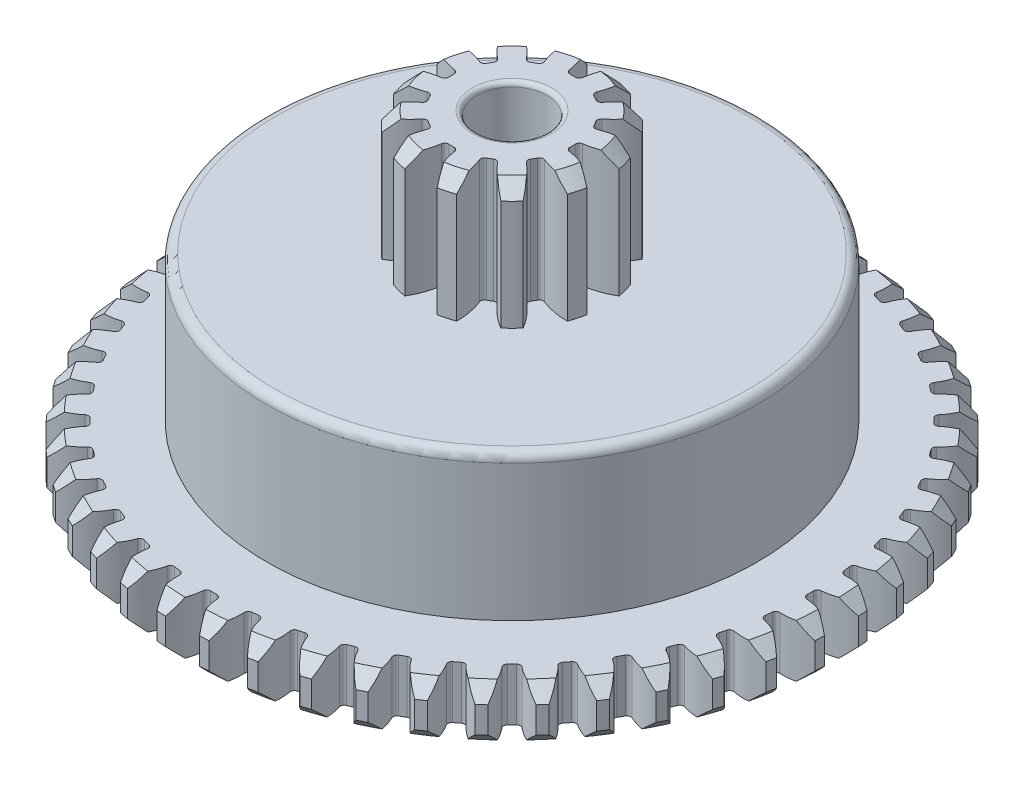
SolidWorks part; units mm, degrees
ref_plane "Front Plane" through (0, 0, 0) normal (0, 0, 1) x (1, 0, 0)
ref_plane "Top Plane" through (0, 0, 0) normal (0, 1, 0) x (1, 0, 0)
ref_plane "Right Plane" through (0, 0, 0) normal (1, 0, 0) x (0, 0, -1)
sketch "Sketch1" plane through (0, 0, 0) normal (0, 1, 0) x (1, 0, 0)
  circle A0 centre (0, 0) radius 1.8 construction
  circle A1 centre (0, 0) radius 2.1
  dimension "D1" = 3.6
  dimension "D2" = 4.2
extrude "Boss-Extrude1" add sketch "Sketch1" along normal blind 2.8
sketch "Sketch2" plane through (0, 2.8, 0) normal (0, 1, 0) x (1, 0, 0)
  line L0 (0, 0) -> (0, 2.1) construction
  line L1 (0, 0) -> (1.05, 1.8187) construction
  line L2 (0, 0) -> (0.5435, 2.0284) construction
  line L3 (-0.1405, 1.3728) -> (0, 0) construction
  line L4 (-0.2349, 1.7846) -> (0.2349, 1.7846) construction
  line L5 (0.2349, 1.7846) -> (0.6888, 1.663) construction
  line L6 (-0.3397, 2.0723) -> (0, 1.1391) construction
  circle A1 centre (0, 0) radius 1.5 construction
  circle A2 centre (0, 0) radius 2.1 construction
  arc A3 (-0.1405, 1.3728) -> (-0.3683, 2.0675) centre (-1.8457, 1.1983) ccw
  arc A4 (0.1405, 1.3728) -> (0.3683, 2.0675) centre (1.8457, 1.1983) cw
  circle A5 centre (0, 0) radius 1.8 construction
  arc A7 (0.1405, 1.3728) -> (-0.1405, 1.3728) centre (0, 0) ccw
  arc A8 (0.3683, 2.0675) -> (-0.3683, 2.0675) centre (0, 0) ccw
  dimension "D1" = 30
  dimension "D4" = 20
extrude "Cut-Extrude1" cut sketch "Sketch2" against normal up to next
fillet "Fillet1" radius 0.09 2 edges at (0.1405, 1.4, -1.3728) (-0.1405, 1.4, -1.3728)
chamfer "Chamfer1" distance 0.3 1 edges at (0, 2.8, 2.1)
pattern_circular "CirPattern1" count 12 over 360 about axis through (0, 2.8, 0) along (0, -1, 0) of "Cut-Extrude1", "Fillet1"
sketch "Sketch3" plane through (0, 0, 0) normal (0, -1, 0) x (1, 0, 0)
  circle A0 centre (0, 0) radius 5.575
  dimension "D1" = 11.15
extrude "Boss-Extrude2" add sketch "Sketch3" along normal blind 3.3
fillet "Fillet2" radius 0.2 1 edges at (0, 0, -5.575)
sketch "Sketch4" plane through (0, -3.3, 0) normal (0, -1, 0) x (1, 0, 0)
  circle A0 centre (0, 0) radius 7.2 construction
  circle A1 centre (0, 0) radius 7.5
  dimension "D1" = 14.4
  dimension "D2" = 15
extrude "Boss-Extrude3" add sketch "Sketch4" along normal blind 1.2
sketch "Sketch8" plane through (0, -4.5, 0) normal (0, -1, 0) x (1, 0, 0)
  line L0 (0, 0) -> (0, 7.5) construction
  line L1 (0, 0) -> (0.9789, 7.4358) construction
  line L2 (0, 0) -> (0.4905, 7.4839) construction
  line L3 (0, 0) -> (-0.1569, 6.7782) construction
  line L4 (-0.2356, 7.1961) -> (0.2356, 7.1961) construction
  line L5 (0.2356, 7.1961) -> (0.7057, 7.1653) construction
  line L6 (-0.3433, 7.4921) -> (0, 6.5489) construction
  circle A0 centre (0, 0) radius 6.9 construction
  circle A2 centre (0, 0) radius 7.5 construction
  arc A3 (-0.1569, 6.7782) -> (-0.3869, 7.49) centre (-1.4672, 6.7479) ccw
  arc A4 (0.1569, 6.7782) -> (0.3869, 7.49) centre (1.4672, 6.7479) cw
  circle A5 centre (0, 0) radius 7.2 construction
  arc A6 (0.3869, 7.49) -> (-0.3869, 7.49) centre (0, 0) ccw
  arc A7 (0.1569, 6.7782) -> (-0.1569, 6.7782) centre (0, 0) ccw
  dimension "D4" = 20
  dimension "D1" = 7.5
extrude "Cut-Extrude3" cut sketch "Sketch8" against normal up to next
fillet "Fillet3" radius 0.09 2 edges at (0.1569, -3.9, 6.7782) (-0.1569, -3.9, 6.7782)
chamfer "Chamfer2" distance 0.3 2 edges at (0, -3.3, -7.5) (0, -4.5, -7.5)
pattern_circular "CirPattern3" count 48 over 360 about axis through (0, -4.5, 0) along (0, 1, 0) of "Cut-Extrude3", "Fillet3" reverse direction yes
sketch "Sketch6" plane through (0, -4.5, 0) normal (0, -1, 0) x (1, 0, 0)
  circle A0 centre (0, 0) radius 4.5
  circle A1 centre (0, 0) radius 7.5 construction
  dimension "D1" = 3
extrude "Cut-Extrude4" cut sketch "Sketch6" against normal blind 3.4
sketch "Sketch7" plane through (0, 2.8, 0) normal (0, 1, 0) x (1, 0, 0)
  circle A0 centre (0, 0) radius 0.8
  dimension "D1" = 1.6
extrude "Cut-Extrude5" cut sketch "Sketch7" against normal through all
fillet "Fillet4" radius 0.1 2 edges at (0, 2.8, 0.8) (0, -4.5, -4.5)
equation "\"Module of small gear\"= 0.3"
equation "\"Number of teeth of small gear\"= 12"
equation "\"Pressure Angle\"= 20"
equation "\"D1@Sketch1\"=\"Module of small gear\" * \"Number of teeth of small gear\""
equation "\"D2@Sketch1\"=(\"Number of teeth of small gear\" + 2) * \"Module of small gear\""
equation "\"D1@Sketch2\"=360 / \"Number of teeth of small gear\""
equation "\"D2@Sketch2\"=\"Module of small gear\" * 2"
equation "\"D4@Sketch2\"=\"Pressure Angle\""
equation "\"D1@Chamfer1\"=\"Module of small gear\""
equation "\"D1@Fillet1\"=0.3 * \"Module of small gear\""
equation "\"D1@CirPattern1\"=\"Number of teeth of small gear\""
equation "\"Module of big gear\"= 0.3"
equation "\"Number of teeth of big gear\"= 48"
equation "\"D1@Sketch4\"=\"Module of big gear\" * \"Number of teeth of big gear\""
equation "\"D2@Sketch4\"=(\"Number of teeth of big gear\" + 2) * \"Module of big gear\""
equation "\"D1@Fillet3\"=0.3 * \"Module of big gear\""
equation "\"D1@Chamfer2\"=\"Module of big gear\""
equation "\"D1@CirPattern2\"=\"Number of teeth of big gear\""
equation "\"D1@Sketch8\"=360 / \"Number of teeth of big gear\""
equation "\"D2@Sketch8\"=\"Module of big gear\" * 2"
equation "\"D4@Sketch8\"=\"Pressure Angle\""
equation "\"D1@CirPattern3\"=\"Number of teeth of big gear\""
